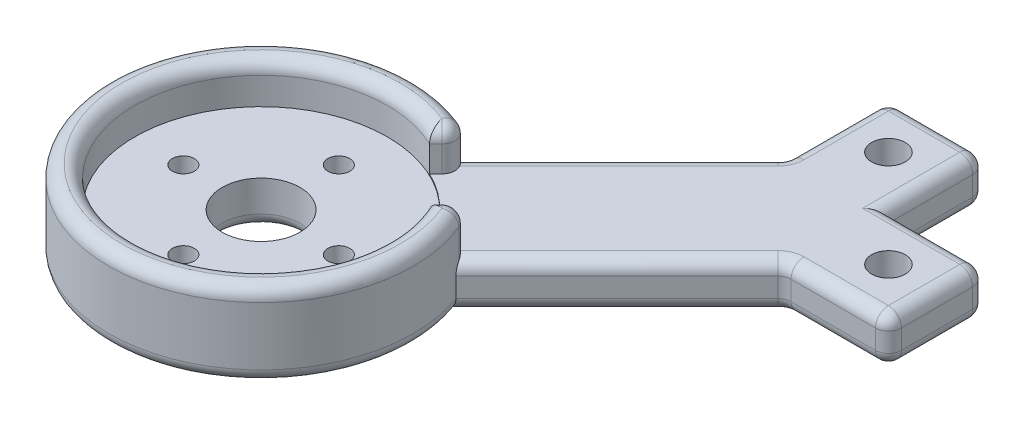
SolidWorks part; units mm, degrees
ref_plane "Front Plane" through (0, 0, 0) normal (0, 0, 1) x (1, 0, 0)
ref_plane "Top Plane" through (0, 0, 0) normal (0, 1, 0) x (1, 0, 0)
ref_plane "Right Plane" through (0, 0, 0) normal (1, 0, 0) x (0, 0, -1)
sketch "Sketch1" plane through (0, 0, 0) normal (0, 1, 0) x (1, 0, 0)
  line L1 (0, 0) -> (15, 0)
  line L2 (0, 0) -> (0, 15)
  line L3 (0, 15) -> (15, 15)
  line L4 (15, 0) -> (15, 15)
  dimension "D1" = 15
  dimension "D2" = 15
extrude "Boss-Extrude1" add sketch "Sketch1" along normal blind 3.5
sketch "Sketch2" plane through (0, 3.5, 0) normal (0, 1, 0) x (1, 0, 0)
  line L1 (15, 15) -> (7.5, 15)
  line L2 (15, 15) -> (15, 7.5)
  line L3 (15, 7.5) -> (7.5, 7.5)
  line L4 (7.5, 15) -> (7.5, 7.5)
  dimension "D1" = 7.5
  dimension "D2" = 7.5
extrude "Cut-Extrude1" cut sketch "Sketch2" against normal through all
sketch "Sketch3" plane through (0, 3.5, 0) normal (0, 1, 0) x (1, 0, 0)
  line L0 (7.5, 15) -> (7.5, 7.5) construction
  line L1 (7.5, 15) -> (0, 15) construction
  circle A0 centre (3.75, 11.25) radius 1.3
  dimension "D1" = 2.6
  dimension "D2" = 3.75
  dimension "D3" = 3.75
extrude "Cut-Extrude2" cut sketch "Sketch3" against normal through all
ref_plane "Plane1" through (0, 0, 0) normal (0.7071, 0, 0.7071) x (0.7071, 0, -0.7071)
mirror "Mirror1" about plane through (0, 0, 0) normal (0.7071, 0, 0.7071) of "Cut-Extrude2"
sketch "Sketch6" plane through (0, 3.5, 0) normal (0, 1, 0) x (1, 0, 0)
  line L0 (0, 7.0711) -> (-12.7279, -5.6569)
  line L1 (0, 15) -> (0, 0) construction
  line L2 (0, 0) -> (15, 0) construction
  line L3 (7.0711, 0) -> (-5.6569, -12.7279)
  line L5 (0, 7.0711) -> (7.0711, 0)
  line L7 (-12.7279, -5.6569) -> (-5.6569, -12.7279)
  dimension "D1" = 7.0711
  dimension "D2" = 7.0711
  dimension "D4" = 10
  dimension "D5" = 18
  dimension "D6" = 18
extrude "Boss-Extrude3" add sketch "Sketch6" against normal blind 3.5
sketch "Sketch7" plane through (0, 3.5, 0) normal (0, 1, 0) x (1, 0, 0)
  circle A0 centre (-16.7111, -16.7111) radius 11.75
  dimension "D1" = 23.5
extrude "Boss-Extrude4" add sketch "Sketch7" against normal blind 3.5
sketch "Sketch8" plane through (0, 3.5, 0) normal (0, 1, 0) x (1, 0, 0)
  circle A0 centre (-16.7111, -16.7111) radius 11.75
  arc A1 (-12.7279, -5.6569) -> (-5.6569, -12.7279) centre (-16.7111, -16.7111) ccw construction
  dimension "D1" = 0
extrude "Boss-Extrude5" add sketch "Sketch8" along normal blind 3
sketch "Sketch9" plane through (0, 6.5, 0) normal (0, 1, 0) x (1, 0, 0)
  circle A0 centre (-16.7111, -16.7111) radius 9.75
  circle A1 centre (-16.7111, -16.7111) radius 11.75 construction
  dimension "D1" = 19.5
  dimension "D2" = 0
extrude "Cut-Extrude3" cut sketch "Sketch9" against normal blind 3.1
fillet "Fillet8" radius 1 1 edges at (15, 0, -3.75)
fillet "Fillet9" radius 1 1 edges at (3.75, 0, -15)
sketch "Sketch12" plane through (0, 3.4, 0) normal (0, 1, 0) x (1, 0, 0)
  circle A0 centre (-16.7111, -16.7111) radius 3
  circle A1 centre (-16.7111, -16.7111) radius 9.75 construction
  dimension "D1" = 0
  dimension "D2" = 6
extrude "Cut-Extrude6" cut sketch "Sketch12" against normal through all
fillet "Fillet23" radius 1 3 edges at (7.5, 2.25, -15) (7.5, 0.2929, -14.7071) (7.5, 0, -10.75)
fillet "Fillet24" radius 1 3 edges at (15, 2.25, -7.5) (14.7071, 0.2929, -7.5) (10.25, 0, -7.5)
fillet "Fillet25" radius 1 3 edges at (15, 3.5, -3.25) (14.7071, 3.5, -7.2071) (10.75, 3.5, -7.5)
sketch "Sketch27" plane through (0, 3.5, 0) normal (0, 1, 0) x (1, 0, 0)
  line L0 (-8.4026, -3.8064) -> (-3.8064, -8.4026)
  line L1 (-3.8064, -8.4026) -> (-10.8775, -15.4737)
  line L2 (-10.8775, -15.4737) -> (-15.4737, -10.8775)
  line L3 (-15.4737, -10.8775) -> (-8.4026, -3.8064)
  line L10 (0, 7.0711) -> (-12.7279, -5.6569) construction
  circle A1 centre (-16.7111, -16.7111) radius 3 construction
  dimension "D1" = 6.5
  dimension "D2" = 1.75
  dimension "D3" = 10
  dimension "D4" = 5
extrude "Cut-Extrude7" cut sketch "Sketch27" along direction (0, 1, 0) on the side of the normal through all
fillet "Fillet31" radius 1 3 edges at (3.25, 3.5, -15) (7.2071, 3.5, -14.7071) (7.5, 3.5, -10.25)
fillet "Fillet32" radius 1 6 edges at (-7.1708, 6.5, 11.767) (-25.0196, 6.5, 25.0196) (-11.767, 6.5, 7.1708) (-23.6054, 6.5, 23.6054) (-11.0249, 5, 6.4287) (-6.4287, 5, 11.0249)
sketch "Sketch30" plane through (0, 3.4, 0) normal (0, 1, 0) x (1, 0, 0)
  circle A6 centre (-16.7111, -10.7111) radius 0.85
  circle A7 centre (-10.7111, -16.7111) radius 0.85
  circle A8 centre (-16.7111, -22.7111) radius 0.85
  circle A9 centre (-22.7111, -16.7111) radius 0.85
  dimension "D2" = 1.7
  dimension "D3" = 1.7
  dimension "D4" = 1.7
  dimension "D5" = 1.7
extrude "Cut-Extrude8" cut sketch "Sketch30" against normal blind 3.5
fillet "Fillet33" radius 1 24 edges at (-6.364, 3.5, -0.7071) (0, 3.5, -10.5355) (0, 3.2071, -14.7071) (0, 1.75, -15) (0, 0.2929, -14.7071) (14.7071, 0.2929, 0) (15, 1.75, 0) (14.7071, 3.2071, 0) (3.75, 0, -9.95) (9.95, 0, -3.75) (0, 0, -10.5355) (-6.364, 0, -0.7071) (-25.0196, 0, 25.0196) (0.7071, 0, 6.364) (10.5355, 0, 0) (-16.7111, 0, 19.7111) (0, 1.75, -7.0711) (7.0711, 1.75, 0) (0.7071, 3.5, 6.364) (10.5355, 3.5, 0) (-22.7111, 0, 15.8611) (-16.7111, 0, 21.8611) (-10.7111, 0, 15.8611) (-16.7111, 0, 9.8611)
